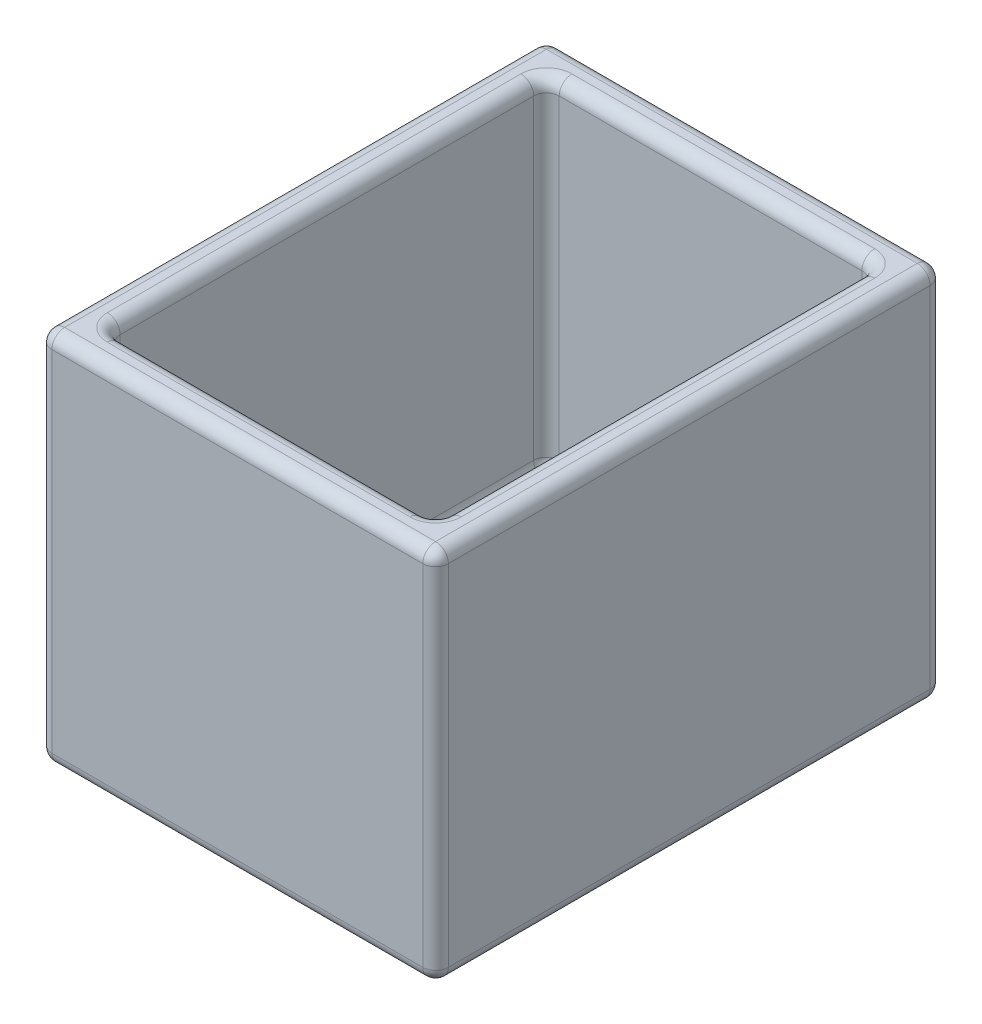
SolidWorks part; units mm, degrees
ref_plane "Front Plane" through (0, 0, 0) normal (0, 0, 1) x (1, 0, 0)
ref_plane "Top Plane" through (0, 0, 0) normal (0, 1, 0) x (1, 0, 0)
ref_plane "Right Plane" through (0, 0, 0) normal (1, 0, 0) x (0, 0, -1)
sketch "Sketch1" plane through (0, 0, 0) normal (0, 1, 0) x (1, 0, 0)
  line L1 (19.25, -25.75) -> (-19.25, -25.75)
  line L2 (19.25, -25.75) -> (19.25, 25.75)
  line L3 (19.25, 25.75) -> (-19.25, 25.75)
  line L4 (-19.25, -25.75) -> (-19.25, 25.75)
  line L5 (19.25, -25.75) -> (-19.25, 25.75) construction
  line L6 (19.25, 25.75) -> (-19.25, -25.75) construction
  point P0 (0, 0)
  dimension "D1" = 51.5
  dimension "D2" = 38.5
extrude "Boss-Extrude1" add sketch "Sketch1" along normal blind 40
shell "Shell1" thickness 4 removed face at (0, 40, 0) outward yes
sketch "Sketch2" plane through (0, 0, -29.75) normal (0, 0, -1) x (-1, 0, 0)
  line L3 (-23.25, -4) -> (23.25, -4) construction
  circle A1 centre (0, 6) radius 2.5
  dimension "D1" = 5
  dimension "D2" = 10
extrude "Cut-Extrude3" cut sketch "Sketch2" against normal up to surface (4 mm away) from surface up to face at (0, 20, -25.75) starting at face at (0, 18, -29.75)
sketch "Sketch3" plane through (0, 0, 0) normal (0, 1, 0) x (1, 0, 0)
  line L0 (0, 25.75) -> (0, -25.75) construction
  line L1 (19.25, 25.75) -> (-19.25, 25.75) construction
  line L2 (-19.25, -25.75) -> (19.25, -25.75) construction
  line L6 (-19.25, 0) -> (19.25, 0) construction
  line L7 (-19.25, 25.75) -> (-19.25, -25.75) construction
  line L8 (19.25, -25.75) -> (19.25, 25.75) construction
fillet "Fillet2" radius 1.5 24 edges at (23.25, 18, -29.75) (23.25, 18, 29.75) (-23.25, 18, 29.75) (0, -4, 29.75) (23.25, -4, 0) (-23.25, -4, 0) (-23.25, 18, -29.75) (0, -4, -29.75) (0, 40, -29.75) (0, 40, -25.75) (-23.25, 40, 0) (-19.25, 40, 0) (0, 40, 29.75) (0, 40, 25.75) (19.25, 40, 0) (23.25, 40, 0) (-19.25, 20, 25.75) (19.25, 20, -25.75) (-19.25, 20, -25.75) (19.25, 20, 25.75) (19.25, 0, 0) (0, 0, 25.75) (-19.25, 0, 0) (0, 0, -25.75)
sketch "Sketch5" plane through (0, 0, 0) normal (0, 1, 0) x (1, 0, 0)
  line L0 (-19.25, -25.75) -> (19.25, -25.75) construction
  line L2 (-19.25, 25.75) -> (-19.25, -25.75) construction
  circle A0 centre (-4.25, -16.25) radius 2
  point P6 (-19.25, -15.2085)
  dimension "D1" = 4
  dimension "D2" = 9.5
  dimension "D3" = 15
extrude "Cut-Extrude4" cut sketch "Sketch5" against normal through all
